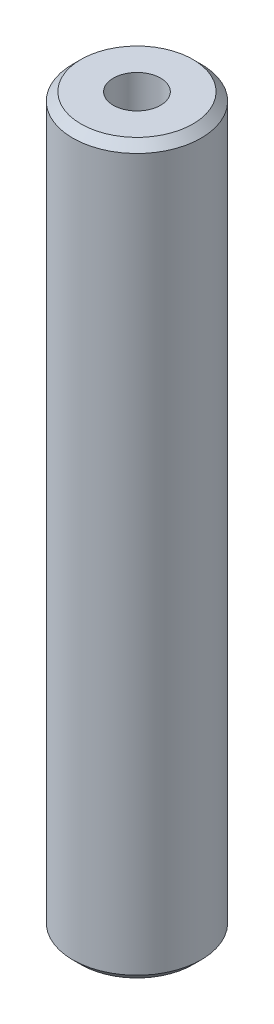
SolidWorks part; units mm, degrees
ref_plane "Front Plane" through (0, 0, 0) normal (0, 0, 1) x (1, 0, 0)
ref_plane "Top Plane" through (0, 0, 0) normal (0, 1, 0) x (1, 0, 0)
ref_plane "Right Plane" through (0, 0, 0) normal (1, 0, 0) x (0, 0, -1)
sketch "Sketch1" plane through (0, 0, 0) normal (0, 1, 0) x (1, 0, 0)
  circle A0 centre (0, 0) radius 27.5
  dimension "SHAFT_OD" = 55
extrude "Boss-Extrude1" add sketch "Sketch1" along normal blind 312.0844
sketch "Sketch2" plane through (0, 0, 0) normal (0, 1, 0) x (1, 0, 0)
  circle A0 centre (0, 0) radius 10.1256
  dimension "BORE_D" = 20.2512
extrude "Cut-Extrude1" cut sketch "Sketch2" along normal through all
chamfer "Chamfer1" distance 3.5082 angle 45 2 edges at (0, 312.0844, 27.5) (0, 0, 27.5)
